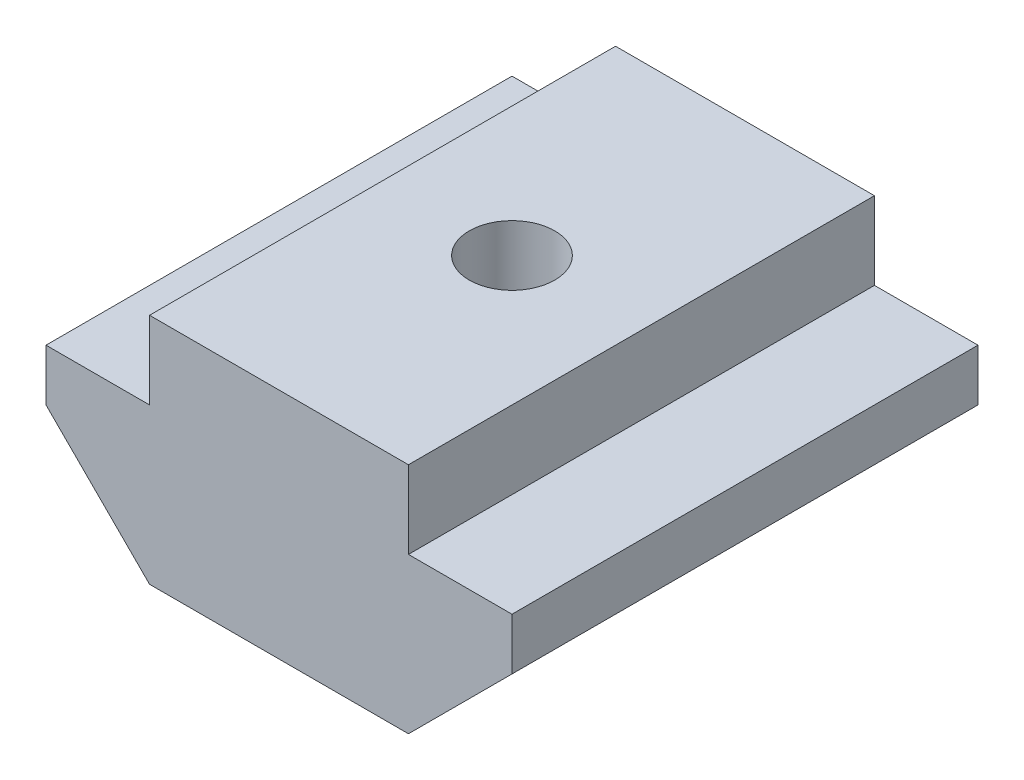
SolidWorks part; units mm, degrees
ref_plane "前视基准面" through (0, 0, 0) normal (0, 0, 1) x (1, 0, 0)
ref_plane "上视基准面" through (0, 0, 0) normal (0, 1, 0) x (1, 0, 0)
ref_plane "右视基准面" through (0, 0, 0) normal (1, 0, 0) x (0, 0, -1)
sketch "草图1" plane through (0, 0, 0) normal (0, 0, 1) x (1, 0, 0)
  line L0 (0, 0) -> (4, 0)
  line L1 (4, 0) -> (4, 3)
  line L2 (4, 3) -> (14, 3)
  line L3 (14, 3) -> (14, 0)
  line L4 (14, 0) -> (18, 0)
  line L5 (18, 0) -> (18, -2)
  line L6 (18, -2) -> (14, -6)
  line L7 (14, -6) -> (4, -6)
  line L8 (4, -6) -> (0, -2)
  line L9 (0, -2) -> (0, 0)
  dimension "D1" = 6
  dimension "D2" = 4
  dimension "D3" = 4
  dimension "D4" = 4
  dimension "D5" = 10
  dimension "D6" = 9
  dimension "D7" = 10
  dimension "D8" = 18
  dimension "D9" = 4
extrude "拉伸1" add sketch "草图1" along normal blind 18
hole_wizard "M4 螺纹孔1" positions "3D草图1" profile "草图2" tap size "M4" standard "GB" end condition through all
sketch3d "3D草图1"
  line L0 (14, 3, 18) -> (14, 3, 0) construction
  point P0 (9, 3, 9)
  dimension "D1" = 5
  dimension "D2" = 9
sketch "草图2" plane through (9, 3, 9) normal (1, 0, 0) x (0, 0, 1)
  line L0 (0, 0) -> (0, 9)
  line L1 (0, 9) -> (1.65, 9)
  line L2 (1.65, 9) -> (1.65, 0)
  line L5 (1.65, 0) -> (0, 0)
  line L11 (0, -6.35) -> (0, 107.95) construction
  dimension "籵謂蹟恇謂郰芛眻噤" = 3.3
  dimension "籵謂蹟恇謂郰芛旮僅" = 9
cosmetic thread "孔螺蚊线1" parameters "D2"=4
